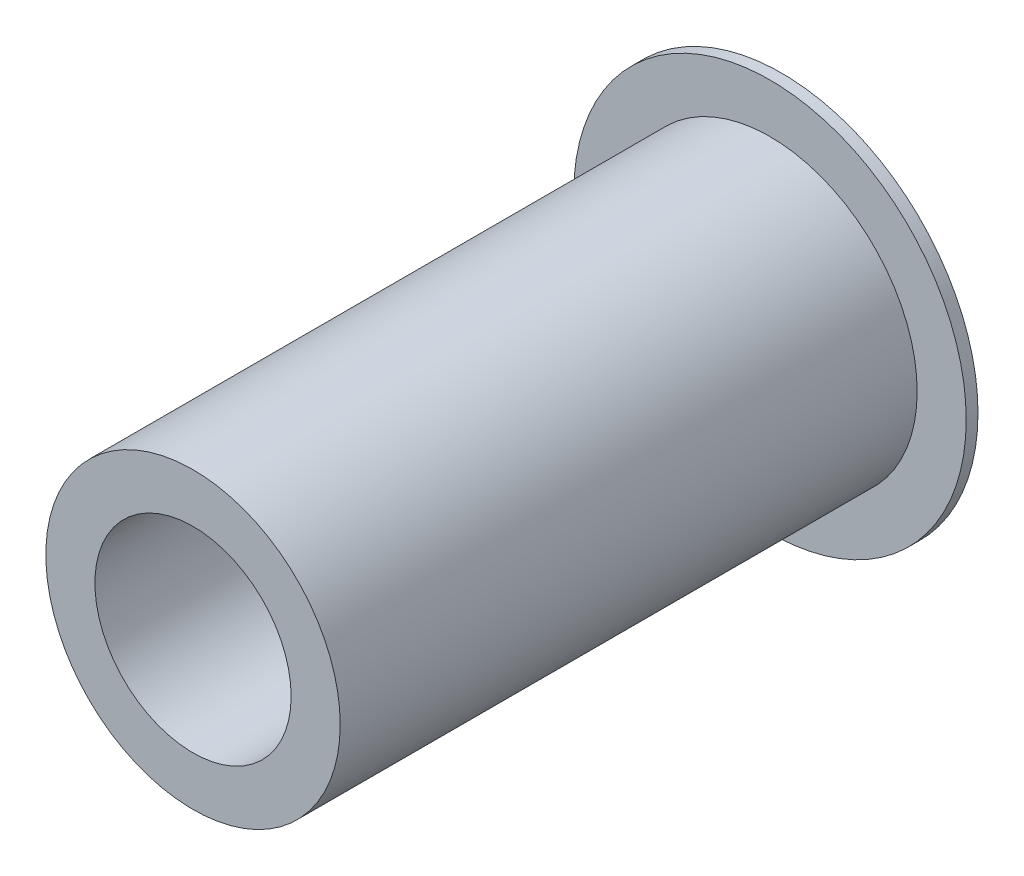
SolidWorks part; units mm, degrees
ref_plane "xy_plane" through (0, 0, 0) normal (0, 0, 1) x (1, 0, 0)
ref_plane "zx_plane" through (0, 0, 0) normal (0, 1, 0) x (1, 0, 0)
ref_plane "yz_plane" through (0, 0, 0) normal (1, 0, 0) x (0, 0, -1)
ref_plane "xMid_plane" through (0, 0, 0) normal (1, 0, 0) x (0, 0, -1)
ref_plane "xMin_plane" through (-0.6173, 0, 0) normal (1, 0, 0) x (0, 0, -1)
ref_plane "xMax_plane" through (0.6173, 0, 0) normal (1, 0, 0) x (0, 0, -1)
ref_plane "yMid_plane" through (0, 0, 0) normal (0, 1, 0) x (1, 0, 0)
ref_plane "yMin_plane" through (0, -0.6173, 0) normal (0, 1, 0) x (1, 0, 0)
ref_plane "yMax_plane" through (0, 0.6173, 0) normal (0, 1, 0) x (1, 0, 0)
ref_plane "zMid_plane" through (0, 0, 0) normal (0, 0, 1) x (1, 0, 0)
ref_plane "zMin_plane" through (0, 0, -0.6173) normal (0, 0, 1) x (1, 0, 0)
ref_plane "zMax_plane" through (0, 0, 0.6173) normal (0, 0, 1) x (1, 0, 0)
ref_axis "x_axis" through (-80.9, 0, 0) along (1, 0, 0)
ref_axis "y_axis" through (0, -50, 0) along (0, 1, 0)
ref_axis "z_axis" through (0, 0, -80.9) along (0, 0, 1)
sketch "Sketch1" plane through (0, 0, 0) normal (0, 0, 1) x (1, 0, 0)
  circle A0 centre (0, 0) radius 37.5
  dimension "D1" = 75
extrude "Boss-Extrude1" add sketch "Sketch1" along normal blind 150
sketch "Sketch2" plane through (0, 0, 0) normal (0, 0, 1) x (1, 0, 0)
  circle A0 centre (0, 0) radius 25
  dimension "D1" = 50
extrude "Cut-Extrude1" cut sketch "Sketch2" against normal offset from surface (145 mm away) 5 from surface up to face at (37.5, 0, 0) starting at face at (37.5, 0, 150)
sketch "Sketch3" plane through (0, 0, 0) normal (0, 0, 1) x (1, 0, 0)
  circle A0 centre (0, 0) radius 50
  dimension "D1" = 100
extrude "Boss-Extrude2" add sketch "Sketch3" along normal blind 3
equation "\"D1@xMin_plane\"=\"externalParameters.this.extentX\"/2"
equation "\"D1@xMax_plane\"=\"externalParameters.this.extentX\"/2"
equation "\"D1@yMin_plane\"=\"externalParameters.this.extentY\"/2"
equation "\"D1@yMax_plane\"=\"externalParameters.this.extentY\"/2"
equation "\"D1@zMin_plane\"=\"externalParameters.this.extentZ\"/2"
equation "\"D1@zMax_plane\"=\"externalParameters.this.extentZ\"/2"
